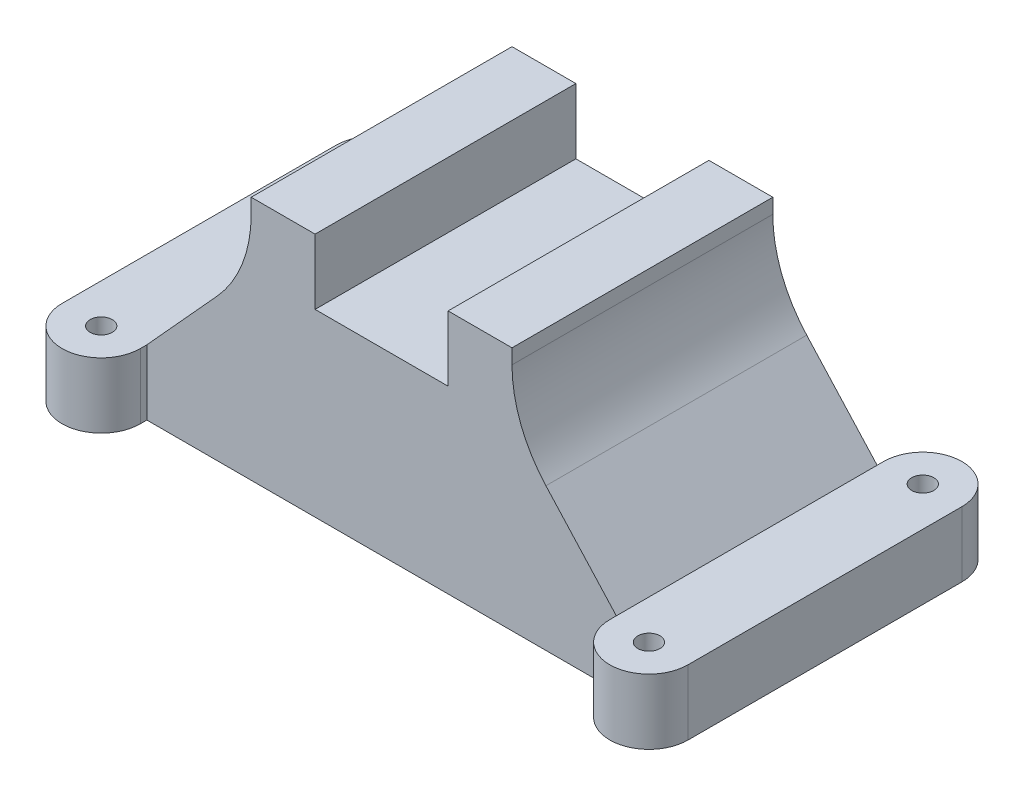
SolidWorks part; units mm, degrees
ref_plane "正面" through (0, 0, 0) normal (0, 0, 1) x (1, 0, 0)
ref_plane "平面" through (0, 0, 0) normal (0, 1, 0) x (1, 0, 0)
ref_plane "右側面" through (0, 0, 0) normal (1, 0, 0) x (0, 0, -1)
sketch "ｽｹｯﾁ1" plane through (0, 0, 0) normal (0, 1, 0) x (1, 0, 0)
  line L0 (-21, 10.5) -> (-21, -10.5) construction
  line L1 (21, -10.5) -> (-21, -10.5) construction
  line L2 (21, -10.5) -> (21, 10.5) construction
  line L3 (21, 10.5) -> (-21, 10.5) construction
  line L4 (-21, -10.5) -> (-21, 10.5) construction
  line L5 (21, -10.5) -> (-21, 10.5) construction
  line L6 (21, 10.5) -> (-21, -10.5) construction
  line L7 (-18, 10.5) -> (-18, -10.5)
  line L8 (-24, 10.5) -> (-24, -10.5)
  line L9 (21, -10.5) -> (21, 10.5) construction
  line L10 (18, -10.5) -> (18, 10.5)
  line L11 (24, -10.5) -> (24, 10.5)
  line L12 (-18, 10.5) -> (18, 10.5)
  line L13 (-18, -10.5) -> (18, -10.5)
  circle A0 centre (-21, 10.5) radius 0.85
  circle A1 centre (-21, -10.5) radius 0.85
  circle A2 centre (21, -10.5) radius 0.85
  circle A3 centre (21, 10.5) radius 0.85
  arc A4 (-18, 10.5) -> (-24, 10.5) centre (-21, 10.5) ccw
  arc A5 (-24, -10.5) -> (-18, -10.5) centre (-21, -10.5) ccw
  arc A6 (18, -10.5) -> (24, -10.5) centre (21, -10.5) ccw
  arc A7 (24, 10.5) -> (18, 10.5) centre (21, 10.5) ccw
  point P0 (0, 0)
  point P10 (-21, 0)
  point P15 (21, 0)
  dimension "D1" = 1.7
  dimension "D4" = 3
  dimension "D2" = 21
  dimension "D3" = 42
extrude "ﾎﾞｽ - 押し出し1" add sketch "ｽｹｯﾁ1" along normal blind 5 contours L8 A5 L7 A4 A0 A1 | L11 A7 L10 A6 A2 A3 region at (-21, 0, 0) region at (21, 0, 0)
sketch "ｽｹｯﾁ2" plane through (0, 0, 0) normal (0, 0, 1) x (1, 0, 0)
  line L0 (-18, 5) -> (-18, 0)
  line L1 (-18, 0) -> (18, 0)
  line L2 (18, 0) -> (24, 0) construction
  line L3 (18, 5) -> (18, 0) construction
  line L4 (18, 0) -> (18, 5)
  line L5 (24, 5) -> (18, 5) construction
  line L6 (18, 5) -> (10, 13.8)
  line L7 (10, 13.8) -> (-10, 13.8)
  line L8 (-10, 13.8) -> (-18, 5)
  line L9 (0, 13.8) -> (0, 0) construction
  dimension "D1" = 13.8
  dimension "D2" = 20
extrude "ﾎﾞｽ - 押し出し2" add sketch "ｽｹｯﾁ2" along normal mid plane 20
sketch "ｽｹｯﾁ3" plane through (0, 0, 0) normal (0, 0, 1) x (1, 0, 0)
  line L0 (-10, 13.8) -> (-10, 18.8)
  line L1 (-10, 18.8) -> (-5.1, 18.8)
  line L2 (-5.1, 18.8) -> (-5.1, 13.8)
  line L3 (10, 13.8) -> (-10, 13.8) construction
  line L4 (-5.1, 13.8) -> (-10, 13.8)
  line L5 (0, -2.75) -> (0, 2.75) construction
  line L6 (5.1, 18.8) -> (5.1, 13.8)
  line L7 (10, 18.8) -> (5.1, 18.8)
  line L8 (10, 13.8) -> (10, 18.8)
  line L9 (5.1, 13.8) -> (10, 13.8)
  dimension "D1" = 10.2
  dimension "D2" = 5
extrude "ﾎﾞｽ - 押し出し3" add sketch "ｽｹｯﾁ3" along normal blind 10 and the other way blind 10
fillet "ﾌｨﾚｯﾄ1" radius 10 2 edges at (10, 13.8, 0) (-10, 13.8, 0)
